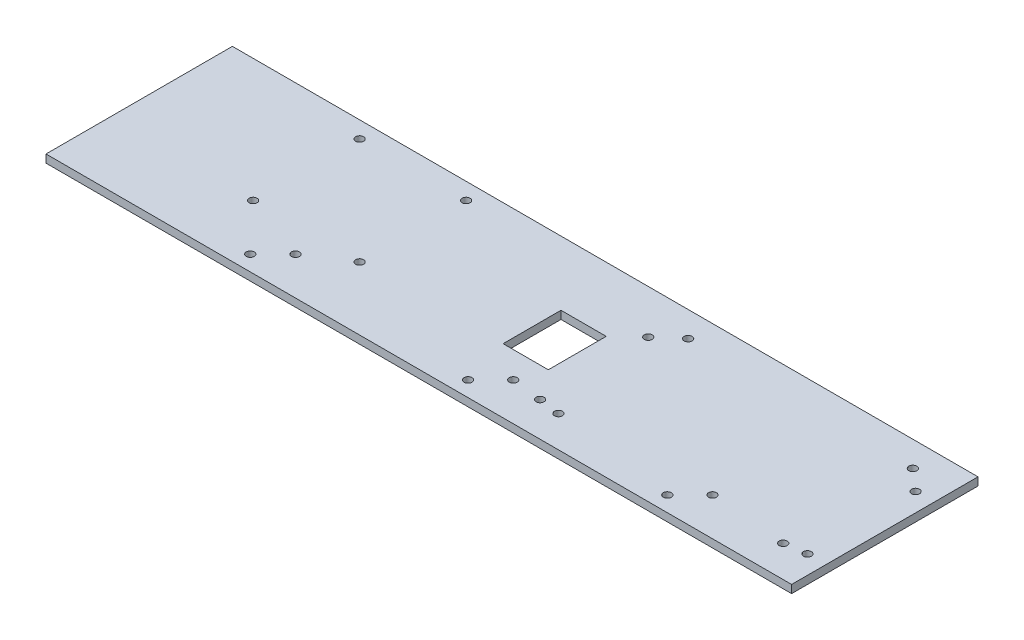
SolidWorks part; units mm, degrees
ref_plane "Front Plane" through (0, 0, 0) normal (0, 0, 1) x (1, 0, 0)
ref_plane "Top Plane" through (0, 0, 0) normal (0, 1, 0) x (1, 0, 0)
ref_plane "Right Plane" through (0, 0, 0) normal (1, 0, 0) x (0, 0, -1)
sketch "Sketch1" plane through (0, 0, 0) normal (0, 1, 0) x (1, 0, 0)
  line L1 (-140, -35) -> (140, -35)
  line L2 (-140, -35) -> (-140, 35)
  line L3 (-140, 35) -> (140, 35)
  line L4 (140, -35) -> (140, 35)
  line L5 (-140, -35) -> (140, 35) construction
  line L6 (-140, 35) -> (140, -35) construction
  line L7 (7.5311, 10.8666) -> (24.5017, 10.8666)
  line L8 (7.5311, 10.8666) -> (7.5311, -10.8666)
  line L9 (7.5311, -10.8666) -> (24.5017, -10.8666)
  line L10 (24.5017, 10.8666) -> (24.5017, -10.8666)
  line L11 (7.5311, 10.8666) -> (24.5017, -10.8666) construction
  line L12 (7.5311, -10.8666) -> (24.5017, 10.8666) construction
  circle A1 centre (87.5712, -29.2426) radius 1.5
  circle A2 centre (96.0565, -20.7574) radius 1.5
  circle A6 centre (133.0434, 18.5) radius 1.5 construction
  circle A9 centre (32.6434, 18.5) radius 1.5
  circle A10 centre (12.7294, -29.2426) radius 1.5
  circle A11 centre (21.2147, -20.7574) radius 1.5
  circle A12 centre (-60.5678, -20.7574) radius 1.5
  circle A13 centre (-69.0531, -29.2426) radius 1.5
  circle A14 centre (40.6434, 25.5) radius 1.5
  circle A15 centre (32.6434, -22.1) radius 1.5
  circle A16 centre (40.6434, -23.2) radius 1.5
  circle A17 centre (125.0434, -23.2) radius 1.5
  circle A18 centre (133.0434, -22.1) radius 1.5
  circle A19 centre (133.0434, 18.5) radius 1.5
  circle A20 centre (125.0434, 25.5) radius 1.5
  circle A21 centre (-85.9926, 28.7487) radius 1.5
  circle A22 centre (-45.9926, 28.7487) radius 1.5
  circle A23 centre (-45.9926, -11.2513) radius 1.5
  circle A24 centre (-85.9926, -11.2513) radius 1.5
  point P0 (0, 0)
  point P14 (16.0164, 0)
  point P66 (16.0164, 0.9)
  dimension "D3" = 3
  dimension "D4" = 3
  dimension "D5" = 3
  dimension "D6" = 3
  dimension "D7" = 3
  dimension "D8" = 3
  dimension "D9" = 3
  dimension "D10" = 3
  dimension "D11" = 3
  dimension "D12" = 3
  dimension "D13" = 3
  dimension "D14" = 3
  dimension "D15" = 3
  dimension "D1" = 280
  dimension "D2" = 70
extrude "Boss-Extrude1" add sketch "Sketch1" along normal blind 3
